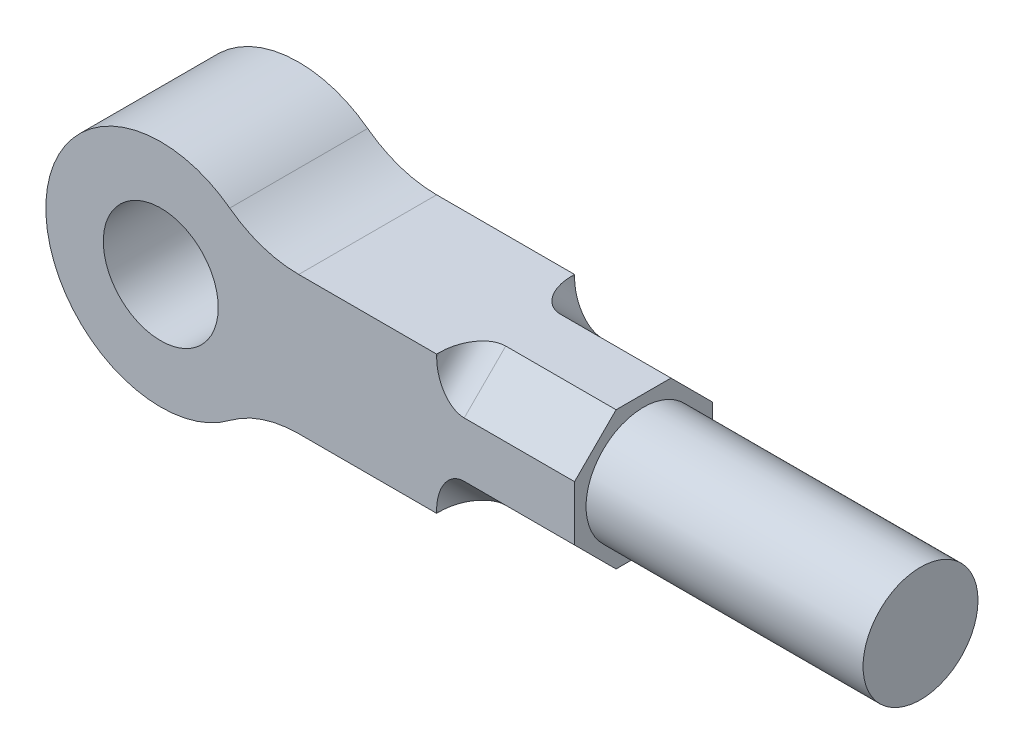
SolidWorks part; units mm, degrees
ref_plane "Front Plane" through (0, 0, 0) normal (0, 0, 1) x (1, 0, 0)
ref_plane "Top Plane" through (0, 0, 0) normal (0, 1, 0) x (1, 0, 0)
ref_plane "Right Plane" through (0, 0, 0) normal (1, 0, 0) x (0, 0, -1)
sketch "Sketch1" plane through (0, 0, 0) normal (0, 0, 1) x (1, 0, 0)
  line L1 (40, 30) -> (180, 30)
  line L3 (40, -30) -> (180, -30)
  line L4 (180, 30) -> (180, -30)
  circle A0 centre (0, 0) radius 25
  arc A1 (40, 30) -> (40, -30) centre (0, 0) ccw
  dimension "D1" = 100
  dimension "D2" = 50
  dimension "D3" = 140
  dimension "D4" = 60
extrude "Boss-Extrude1" add sketch "Sketch1" along normal blind 60
fillet "Fillet1" radius 50 2 edges at (40, -30, 30) (40, 30, 30)
sketch "Sketch2" plane through (180, 0, 0) normal (1, 0, 0) x (0, 0, -1)
  line L0 (0, -30) -> (0, 30) construction
  line L1 (0, 11.94) -> (-18.06, 30)
  line L2 (-60, 30) -> (0, 30) construction
  line L3 (-18.06, 30) -> (0, 30)
  line L4 (0, 30) -> (0, 11.94)
  line L5 (-18.06, -30) -> (0, -11.94)
  line L6 (0, -30) -> (-18.06, -30)
  line L7 (0, -11.94) -> (0, -30)
  line L8 (-60, -11.94) -> (-41.94, -30)
  line L9 (-60, -30) -> (-60, -11.94)
  line L10 (-41.94, -30) -> (-60, -30)
  line L11 (-41.94, 30) -> (-60, 11.94)
  line L12 (-60, 30) -> (-41.94, 30)
  line L13 (-60, 11.94) -> (-60, 30)
  circle A0 centre (-30, 0) radius 25
  point P23 (-30, 0)
  dimension "D1" = 50
  dimension "D2" = 30
  dimension "D3" = 18.06
  dimension "D4" = 18.06
  dimension "D5" = 4
extrude "Cut-Extrude1" cut sketch "Sketch2" against normal blind 60 contours L11 L13 L12 | L4 L1 L3 | L5 L7 L6 | L8 L10 L9
extrude "Boss-Extrude2" add sketch "Sketch2<4>" along normal blind 120.5 contours A0 region at (180, 0, 30)
sketch "Sketch2<4>" plane through (180, 0, 0) normal (1, 0, 0) x (0, 0, -1) same geometry as "Sketch2"
fillet "Fillet2" radius 12 4 edges at (120, -20.97, 50.97) (120, -20.97, 9.03) (120, 20.97, 9.03) (120, 20.97, 50.97)
